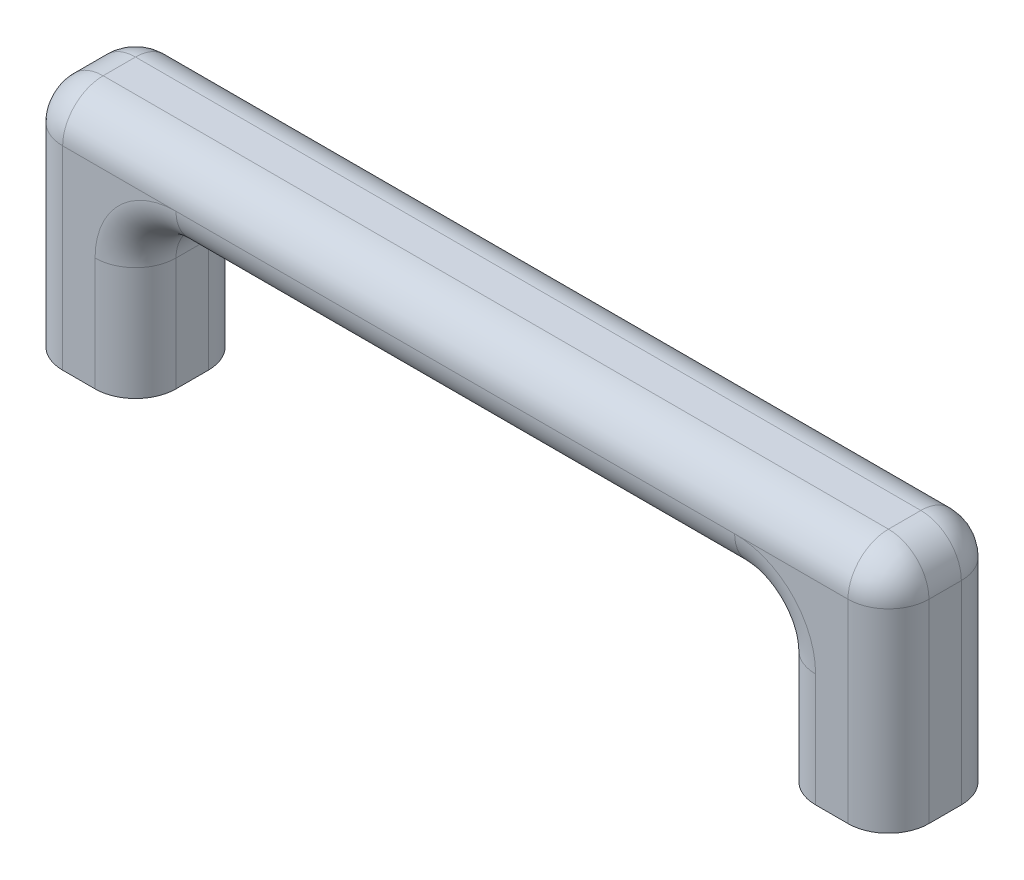
SolidWorks part; units mm, degrees
ref_plane "Plan de face" through (0, 0, 0) normal (0, 0, 1) x (1, 0, 0)
ref_plane "Plan de dessus" through (0, 0, 0) normal (0, 1, 0) x (1, 0, 0)
ref_plane "Plan de droite" through (0, 0, 0) normal (1, 0, 0) x (0, 0, -1)
sketch "Esquisse1" plane through (0, 0, 0) normal (0, 0, 1) x (1, 0, 0)
  line L1 (-53.5, -14.5) -> (53.5, -14.5)
  line L2 (-53.5, -14.5) -> (-53.5, 14.5)
  line L3 (-53.5, 14.5) -> (53.5, 14.5)
  line L4 (53.5, -14.5) -> (53.5, 14.5)
  line L5 (-53.5, -14.5) -> (53.5, 14.5) construction
  line L6 (-53.5, 14.5) -> (53.5, -14.5) construction
  point P0 (0, 0)
  dimension "D1" = 107
  dimension "D2" = 29
extrude "Boss.-Extru.1" add sketch "Esquisse1" along normal blind 14
sketch "Esquisse2" plane through (0, 0, 14) normal (0, 0, 1) x (1, 0, 0)
  line L0 (-53.5, -14.5) -> (53.5, -14.5) construction
  line L1 (-39.5, 4.5) -> (39.5, 4.5)
  line L2 (-39.5, 4.5) -> (-39.5, -14.5)
  line L3 (-39.5, -14.5) -> (39.5, -14.5)
  line L4 (39.5, 4.5) -> (39.5, -14.5)
  line L5 (-39.5, 4.5) -> (39.5, -14.5) construction
  line L6 (-39.5, -14.5) -> (39.5, 4.5) construction
  line L7 (53.5, 14.5) -> (-53.5, 14.5) construction
  line L8 (-53.5, 14.5) -> (-53.5, -14.5) construction
  line L9 (53.5, -14.5) -> (53.5, 14.5) construction
  point P0 (0, -5)
  dimension "D1" = 10
  dimension "D2" = 14
  dimension "D3" = 14
extrude "Enlèv. mat.-Extru.1" cut sketch "Esquisse2" against normal through all
fillet "Congé1" radius 5 16 edges at (53.5, 0, 0) (-53.5, 0, 0) (-39.5, -5, 0) (0, 4.5, 0) (39.5, -5, 0) (-39.5, -5, 14) (-53.5, 0, 14) (53.5, 0, 14) (39.5, -5, 14) (0, 4.5, 14) (53.5, 14.5, 7) (0, 14.5, 14) (-53.5, 14.5, 7) (0, 14.5, 0) (39.5, 4.5, 7) (-39.5, 4.5, 7)
sketch "Esquisse3" plane through (0, -14.5, 0) normal (0, -1, 0) x (1, 0, 0)
  line L0 (-46.5, 14) -> (-46.5, 0) construction
  line L1 (-48.5, 14) -> (-44.5, 14) construction
  line L2 (-48.5, 0) -> (-44.5, 0) construction
  line L3 (46.5, 14) -> (46.5, 0) construction
  line L4 (44.5, 14) -> (48.5, 14) construction
  line L5 (44.5, 0) -> (48.5, 0) construction
  circle A0 centre (-46.5, 7) radius 1.5
  circle A1 centre (46.5, 7) radius 1.5
  dimension "D1" = 3
extrude "Enlèv. mat.-Extru.2" cut sketch "Esquisse3" against normal blind 5
